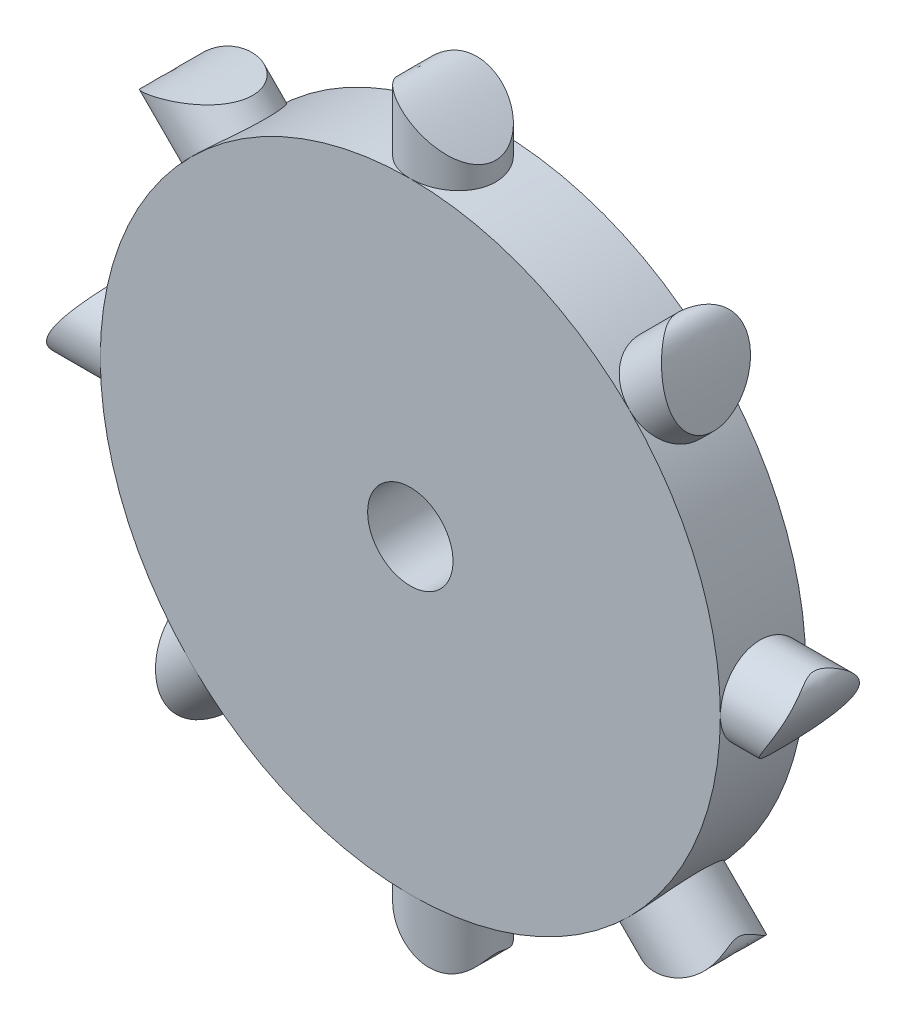
SolidWorks part; units mm, degrees
ref_plane "Front Plane" through (0, 0, 0) normal (0, 0, 1) x (1, 0, 0)
ref_plane "Top Plane" through (0, 0, 0) normal (0, 1, 0) x (1, 0, 0)
ref_plane "Right Plane" through (0, 0, 0) normal (1, 0, 0) x (0, 0, -1)
sketch "Sketch1" plane through (0, 0, 0) normal (0, 0, 1) x (1, 0, 0)
  circle A0 centre (0, 0) radius 27.6693
  dimension "D1" = 55.3385
extrude "Boss-Extrude1" add sketch "Sketch1" along normal blind 7.62
sketch "Sketch3" plane through (0, 0, 0) normal (0, 0, -1) x (-1, 0, 0)
  circle A0 centre (0, 0) radius 3.81
  dimension "D1" = 7.62
extrude "Cut-Extrude2" cut sketch "Sketch3" against normal up to next
ref_plane "Plane1" through (0, 33.02, 0) normal (0, 1, 0) x (1, 0, 0)
sketch "Sketch4" plane through (0, 33.02, 0) normal (0, 1, 0) x (1, 0, 0)
  line L0 (27.6693, 0) -> (-27.6693, 0) construction
  line L1 (-27.6693, -7.62) -> (27.6693, -7.62) construction
  line L2 (0, -55) -> (0, 55) construction
  circle A0 centre (0, -3.81) radius 3.81
extrude "Boss-Extrude3" add sketch "Sketch4" against normal up to next contours A0
sketch "Sketch6" plane through (0, 0, 0) normal (0, 0, -1) x (-1, 0, 0)
  line L3 (4.331, 33.6672) -> (-4.2034, 33.6672)
  line L4 (4.331, 33.6672) -> (4.331, 28.7399)
  line L5 (4.331, 28.7399) -> (3.81, 28.7399)
  line L6 (-4.2034, 33.6672) -> (-4.2034, 28.7399)
  line L7 (3.81, 27.4057) -> (3.81, 33.02) construction
  line L8 (3.81, 27.4057) -> (3.81, 33.02) construction
  spline S1 degree 2 poles (-4.2034, 28.7399) (5.4053, 37.2784) (3.81, 28.7399) knots 0 0 0 1 1 1
extrude "Cut-Extrude3" cut sketch "Sketch6" against normal blind 10.16
pattern_circular "CirPattern1" count 8 over 360 about axis through (0, 0, 7.62) along (0, 0, -1) of "Boss-Extrude3", "Cut-Extrude3"
